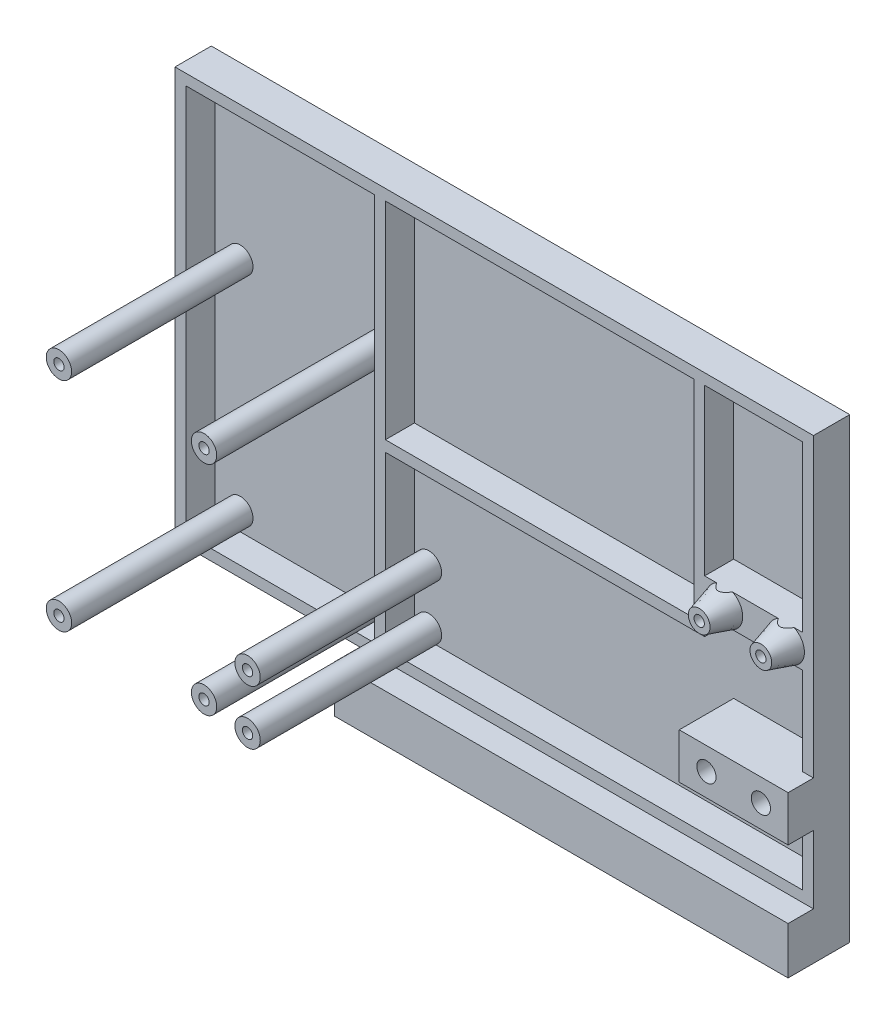
SolidWorks part; units mm, degrees
material "ABS"
ref_plane "Front Plane" through (0, 0, 0) normal (0, 0, 1) x (1, 0, 0)
ref_plane "Top Plane" through (0, 0, 0) normal (0, 1, 0) x (1, 0, 0)
ref_plane "Right Plane" through (0, 0, 0) normal (1, 0, 0) x (0, 0, -1)
sketch "Sketch1" plane through (0, 0, 0) normal (0, 0, 1) x (1, 0, 0)
  line L0 (-45.5, -31.5) -> (-45.5, 31.5) construction
  line L1 (-42.5, -28.5) -> (42.5, -28.5)
  line L2 (-42.5, -28.5) -> (-42.5, 28.5)
  line L3 (-42.5, 28.5) -> (42.5, 28.5)
  line L4 (42.5, -28.5) -> (42.5, 28.5)
  line L5 (-42.5, -28.5) -> (42.5, 28.5) construction
  line L6 (-42.5, 28.5) -> (42.5, -28.5) construction
  line L7 (-45.5, -81.5) -> (75.5, -81.5) construction
  line L8 (-45.5, -81.5) -> (-45.5, -31.5) construction
  line L9 (-45.5, -31.5) -> (75.5, -31.5) construction
  line L10 (75.5, -81.5) -> (75.5, -31.5) construction
  line L11 (-45.5, -81.5) -> (75.5, -31.5) construction
  line L12 (-45.5, -31.5) -> (75.5, -81.5) construction
  line L17 (-45.5, 31.5) -> (45.5, 31.5) construction
  line L18 (45.5, -31.5) -> (45.5, 31.5) construction
  line L19 (-45.5, -31.5) -> (45.5, -31.5) construction
  line L21 (45.5, 31.5) -> (75.5, 31.5) construction
  line L22 (45.5, 31.5) -> (45.5, -31.5) construction
  line L23 (45.5, -31.5) -> (75.5, -31.5) construction
  line L24 (75.5, 31.5) -> (75.5, -31.5) construction
  line L25 (-45.5, 31.5) -> (75.5, 31.5)
  line L26 (-45.5, 31.5) -> (-45.5, -81.5)
  line L27 (-45.5, -81.5) -> (75.5, -81.5)
  line L28 (75.5, 31.5) -> (75.5, -81.5)
  circle A0 centre (68, -56.5) radius 2.65
  circle A1 centre (53, -56.5) radius 2.65
  circle A2 centre (51, -21.5) radius 1.425
  circle A3 centre (68, -21.5) radius 1.425
  point P0 (0, 0)
  point P6 (15, -56.5)
  dimension "D4" = 15
  dimension "D5" = 7.5
  dimension "D6" = 5.3
  dimension "D10" = 2.85
  dimension "D1" = 85
  dimension "D2" = 57
  dimension "D3" = 50
  dimension "D7" = 30
  dimension "D8" = 10
  dimension "D11" = 17
  dimension "D9" = 3
extrude "Boss-Extrude1" add sketch "Sketch1" along normal blind 10
sketch "Sketch2" plane through (0, 0, 0) normal (0, 0, -1) x (-1, 0, 0)
  line L1 (-42.5, 28.5) -> (42.5, 28.5)
  line L2 (-42.5, 28.5) -> (-42.5, -28.5)
  line L3 (-42.5, -28.5) -> (42.5, -28.5)
  line L4 (42.5, 28.5) -> (42.5, -28.5)
extrude "Boss-Extrude2" add sketch "Sketch2" against normal blind 2
sketch "Sketch4" plane through (0, 0, 10) normal (0, 0, 1) x (1, 0, 0)
  line L0 (-42.5, 28.5) -> (-45.5, 31.5) construction
  line L1 (-45.5, 31.5) -> (45.5, 31.5)
  line L2 (-45.5, 31.5) -> (-45.5, -31.5)
  line L3 (-45.5, -31.5) -> (45.5, -31.5)
  line L4 (45.5, 31.5) -> (45.5, -31.5)
  line L5 (42.5, -28.5) -> (45.5, -31.5) construction
  line L6 (-45.5, -31.5) -> (-45.5, -81.5)
  line L7 (-45.5, -81.5) -> (75.5, -81.5)
  line L8 (75.5, -81.5) -> (75.5, 31.5)
  line L9 (75.5, 31.5) -> (45.5, 31.5)
  line L10 (45.5, -31.5) -> (45.5, 31.5)
  line L11 (-45.5, -31.5) -> (45.5, -31.5)
  line L12 (-45.5, -81.5) -> (-45.5, -31.5)
  line L13 (53, -56.5) -> (68, -56.5) construction
  line L14 (-42.5, -28.5) -> (-42.5, -78.5)
  line L15 (45.5, -62.75) -> (75.5, -62.75)
  line L16 (45.5, -62.75) -> (45.5, -50.25)
  line L17 (45.5, -50.25) -> (75.5, -50.25)
  line L18 (75.5, -62.75) -> (75.5, -50.25)
  line L19 (45.5, -62.75) -> (75.5, -50.25) construction
  line L20 (45.5, -50.25) -> (75.5, -62.75) construction
  line L21 (-42.5, -78.5) -> (72.5, -78.5)
  line L22 (72.5, -78.5) -> (72.5, -62.75)
  line L23 (45.5, 28.5) -> (72.5, 28.5)
  line L24 (72.5, 28.5) -> (72.5, -21.5)
  line L25 (72.5, -21.5) -> (72.5, -50.25)
  line L26 (-42.5, -78.5) -> (-45.5, -81.5) construction
  line L27 (72.5, -78.5) -> (75.5, -81.5) construction
  line L28 (72.5, 28.5) -> (75.5, 31.5) construction
  line L29 (51, -21.5) -> (68, -21.5) construction
  line L31 (73.5, -26) -> (45.5, -26)
  line L32 (73.5, -26) -> (73.5, -17)
  line L33 (73.5, -17) -> (45.5, -17)
  line L34 (45.5, -26) -> (45.5, -17)
  line L35 (73.5, -26) -> (45.5, -17) construction
  line L36 (73.5, -17) -> (45.5, -26) construction
  circle A2 centre (53, -56.5) radius 2.65
  circle A3 centre (68, -56.5) radius 2.65
  circle A6 centre (68, -56.5) radius 2.65 construction
  point P21 (60.5, -56.5)
  point P29 (59.5, -21.5)
  dimension "D2" = 9
  dimension "D1" = 12.5
extrude "Cut-Extrude1" cut sketch "Sketch4" against normal up to surface (8 mm away) contours L33 L24 L23 L10 | L25 L31 L4 L11 L14 L21 L22 L15 L16 L17 region at (59, 5.75, 10) region at (13.4057, -54.1556, 10) up to face at (0, 0, 2)
sketch "Sketch5" plane through (0, 0, 0) normal (0, 0, -1) x (-1, 0, 0)
  line L1 (-64.25, -25.25) -> (-71.75, -25.25) construction
  line L2 (-64.25, -25.25) -> (-64.25, -17.75) construction
  line L3 (-64.25, -17.75) -> (-71.75, -17.75) construction
  line L4 (-71.75, -25.25) -> (-71.75, -17.75) construction
  line L5 (-64.25, -25.25) -> (-71.75, -17.75) construction
  line L6 (-64.25, -17.75) -> (-71.75, -25.25) construction
  line L7 (-47.25, -25.25) -> (-54.75, -25.25) construction
  line L8 (-47.25, -25.25) -> (-47.25, -17.75) construction
  line L9 (-47.25, -17.75) -> (-54.75, -17.75) construction
  line L10 (-54.75, -25.25) -> (-54.75, -17.75) construction
  line L11 (-47.25, -25.25) -> (-54.75, -17.75) construction
  line L12 (-47.25, -17.75) -> (-54.75, -25.25) construction
  line L13 (-73.25, -61.75) -> (-62.75, -61.75)
  line L14 (-73.25, -61.75) -> (-73.25, -51.25)
  line L15 (-73.25, -51.25) -> (-62.75, -51.25)
  line L16 (-62.75, -61.75) -> (-62.75, -51.25)
  line L17 (-73.25, -61.75) -> (-62.75, -51.25) construction
  line L18 (-73.25, -51.25) -> (-62.75, -61.75) construction
  line L19 (-47.75, -61.75) -> (-58.25, -61.75)
  line L20 (-47.75, -61.75) -> (-47.75, -51.25)
  line L21 (-47.75, -51.25) -> (-58.25, -51.25)
  line L22 (-58.25, -61.75) -> (-58.25, -51.25)
  line L23 (-47.75, -61.75) -> (-58.25, -51.25) construction
  line L24 (-47.75, -51.25) -> (-58.25, -61.75) construction
  point P0 (-68, -21.5)
  point P6 (-51, -21.5)
  point P12 (-68, -56.5)
  point P18 (-53, -56.5)
  dimension "D1" = 7.5
  dimension "D2" = 10.5
extrude "Cut-Extrude2" cut sketch "Sketch5" against normal blind 7
sketch "Sketch7" plane through (0, 0, 10) normal (0, 0, 1) x (1, 0, 0)
  line L0 (75.5, -81.5) -> (75.5, 31.5) construction
  line L1 (45.5, -50.25) -> (75.5, -50.25)
  line L2 (45.5, -50.25) -> (45.5, -62.75)
  line L3 (45.5, -62.75) -> (75.5, -62.75)
  line L4 (75.5, -50.25) -> (75.5, -62.75)
  line L5 (45.5, -62.75) -> (72.5, -62.75) construction
  circle A0 centre (51, -21.5) radius 1.425
  circle A1 centre (51, -21.5) radius 3
  circle A2 centre (68, -21.5) radius 3
  circle A3 centre (68, -21.5) radius 1.425
  circle A4 centre (53, -56.5) radius 2.65
  circle A5 centre (68, -56.5) radius 2.65
  circle A6 centre (53, -56.5) radius 2.65 construction
  circle A7 centre (51, -21.5) radius 1.425 construction
  dimension "D1" = 6
extrude "Boss-Extrude4" add sketch "Sketch7" along normal blind 7
chamfer "Chamfer2" distance 2 distance2 7 2 edges at (65, -21.5, 10) (48, -21.5, 10) first distance on face at (65, -21.5, 10)
sketch "Sketch9" plane through (0, 0, 0) normal (0, 0, -1) x (-1, 0, 0)
  line L0 (45.5, -81.5) -> (-75.5, -81.5) construction
  line L1 (45.5, 31.5) -> (100.5, 31.5)
  line L2 (45.5, 31.5) -> (45.5, -81.5)
  line L3 (45.5, -81.5) -> (100.5, -81.5)
  line L4 (100.5, 31.5) -> (100.5, -81.5)
  dimension "D1" = 55
extrude "Boss-Extrude5" add sketch "Sketch9" against normal up to surface (17 mm away) up to face at (54, -21.5, 17)
sketch "Sketch10" plane through (0, 0, 17) normal (0, 0, 1) x (1, 0, 0)
  line L1 (-90.5, -73.5) -> (-50.5, -73.5) construction
  line L2 (-90.5, -73.5) -> (-90.5, -13.5) construction
  line L3 (-90.5, -13.5) -> (-50.5, -13.5) construction
  line L4 (-50.5, -73.5) -> (-50.5, -13.5) construction
  line L5 (-90.5, -73.5) -> (-50.5, -13.5) construction
  line L6 (-90.5, -13.5) -> (-50.5, -73.5) construction
  line L7 (-45.5, 31.5) -> (-45.5, -81.5) construction
  line L8 (-45.5, -78.5) -> (-95.5, -78.5) construction
  line L9 (-45.5, -78.5) -> (-45.5, -8.5) construction
  line L10 (-45.5, -8.5) -> (-95.5, -8.5) construction
  line L11 (-95.5, -78.5) -> (-95.5, -8.5) construction
  line L12 (-45.5, -78.5) -> (-95.5, -8.5) construction
  line L13 (-45.5, -8.5) -> (-95.5, -78.5) construction
  line L14 (-45.5, 31.5) -> (-45.5, -81.5) construction
  circle A0 centre (-90.5, -13.5) radius 1.425
  circle A1 centre (-50.5, -13.5) radius 1.425
  circle A2 centre (-90.5, -73.5) radius 1.425
  circle A3 centre (-50.5, -73.5) radius 1.425
  point P0 (-70.5, -43.5)
  point P9 (-70.5, -43.5)
  point P14 (0, 0)
  point P16 (-45.5, -81.5)
  point P17 (-45.5, -76.7867)
  point P21 (0, 0)
  dimension "D3" = 2.85
  dimension "D1" = 60
  dimension "D2" = 40
  dimension "D4" = 50
  dimension "D5" = 70
extrude "Cut-Extrude3" cut sketch "Sketch10" against normal through all
sketch "Sketch11" plane through (0, 0, 17) normal (0, 0, 1) x (1, 0, 0)
  line L0 (-48.5, 28.5) -> (-45.5, 28.5)
  line L1 (-45.5, 31.5) -> (-45.5, -81.5) construction
  line L2 (-48.5, -78.5) -> (-45.5, -78.5)
  line L3 (-45.5, 31.5) -> (-45.5, -81.5) construction
  line L4 (-45.5, -78.5) -> (-45.5, 28.5)
  line L8 (-48.5, -78.5) -> (-48.5, 28.5)
  line L9 (-48.5, 28.5) -> (-97.5, 28.5)
  line L10 (-97.5, 28.5) -> (-97.5, -78.5)
  line L11 (-97.5, -78.5) -> (-48.5, -78.5)
  line L12 (-48.5, -78.5) -> (-48.5, 28.5) construction
  line L13 (-48.5, 28.5) -> (-97.5, 28.5)
  line L14 (-97.5, 28.5) -> (-97.5, -78.5)
  line L15 (-97.5, -78.5) -> (-48.5, -78.5)
  circle A0 centre (-90.5, -13.5) radius 3.5
  circle A1 centre (-50.5, -13.5) radius 3.5
  circle A2 centre (-90.5, -73.5) radius 3.5
  circle A3 centre (-50.5, -73.5) radius 3.5
  line M10 (-45.5, -81.5) -> (-45.5, 31.5)
  dimension "D1" = 7
  dimension "D2" = 3
extrude "Cut-Extrude4" cut sketch "Sketch11" against normal up to surface (15 mm away) contours L15 L12 L13 A1 A0 L14 A2 A3 | L12 L2 L0 M10 region at (-46.9653, -24.2757, 17) region at (-73.0159, -24.4856, 17) up to face at (0, 0, 2)
sketch "Sketch12" plane through (0, 0, 17) normal (0, 0, 1) x (1, 0, 0)
  line L5 (-100.5, -81.5) -> (-45.5, -81.5)
  line L6 (-100.5, -81.5) -> (-100.5, 31.5)
  line L7 (-100.5, 31.5) -> (-45.5, 31.5)
  line L8 (-45.5, -81.5) -> (-45.5, 31.5)
  circle A0 centre (-90.5, -13.5) radius 3.5
  circle A1 centre (-50.5, -13.5) radius 3.5
  circle A2 centre (-90.5, -73.5) radius 3.5
  circle A3 centre (-50.5, -73.5) radius 3.5
  circle A4 centre (-90.5, -73.5) radius 3.5 construction
extrude "Cut-Extrude5" cut sketch "Sketch12" against normal up to surface (7 mm away) up to face at (37.0833, -29.625, 10)
sketch "Sketch14" plane through (0, 0, 2) normal (0, 0, 1) x (1, 0, 0)
  line L8 (-38.5, -75.5) -> (-38.5, -60.5) construction
  line L9 (-42.5, -78.5) -> (-21.5, -78.5) construction
  line L10 (-42.5, -78.5) -> (-42.5, -57.5) construction
  line L11 (-42.5, -57.5) -> (-21.5, -57.5) construction
  line L12 (-21.5, -78.5) -> (-21.5, -57.5) construction
  line L13 (-42.5, -78.5) -> (-21.5, -57.5) construction
  line L14 (-42.5, -57.5) -> (-21.5, -78.5) construction
  circle A0 centre (-38.5, -60.5) radius 1.275
  circle A1 centre (-38.5, -75.5) radius 1.275
  point P0 (-32, -68)
  point P9 (-38.5, -68)
  dimension "D3" = 2.55
  dimension "D1" = 21
  dimension "D2" = 15
  dimension "D4" = 4
extrude "Cut-Extrude6" cut sketch "Sketch14" against normal through all both and the other way through all
sketch "Sketch13" plane through (0, -81.5, 0) normal (0, -1, 0) x (1, 0, 0)
  line L0 (71.5, 4) -> (-45.5, 4) construction
  line L1 (-49.5, 0) -> (75.5, 0)
  line L2 (-49.5, 0) -> (-49.5, 17)
  line L3 (-49.5, 17) -> (75.5, 17)
  line L4 (75.5, 0) -> (75.5, 17)
  line L5 (42.25, 4) -> (-16.25, 4) construction
  line L6 (-100.5, 0) -> (75.5, 0) construction
  line L7 (13, 4) -> (-16.25, 4) construction
  line L8 (-16.25, 4) -> (-45.5, 4) construction
  circle A0 centre (71.5, 4) radius 4 construction
  circle A1 centre (-45.5, 4) radius 4 construction
  circle A2 centre (-16.25, 4) radius 1.9
  circle A3 centre (42.25, 4) radius 1.9
  circle A4 centre (71.5, 4) radius 1.9
  circle A5 centre (-45.5, 4) radius 1.9
  point P9 (13, 4)
  point P12 (13, 4)
  dimension "D1" = 8
  dimension "D3" = 3.8
  dimension "D2" = 125
extrude "Boss-Extrude6" add sketch "Sketch13" along normal blind 13
sketch "Sketch15" plane through (0, 0, 2) normal (0, 0, 1) x (1, 0, 0)
  circle A0 centre (-38.5, -60.5) radius 3.5
  circle A1 centre (-38.5, -75.5) radius 3.5
  circle A2 centre (-38.5, -60.5) radius 1.275
  circle A3 centre (-38.5, -75.5) radius 1.275
  circle A4 centre (-38.5, -60.5) radius 1.275 construction
  dimension "D1" = 7
extrude "Boss-Extrude7" add sketch "Sketch15" along normal up to surface (15 mm away) up to face at (-49.075, -73.5, 17)
sketch "Sketch16" plane through (0, 0, 17) normal (0, 0, 1) x (1, 0, 0)
  circle A0 centre (-90.5, -13.5) radius 1.425
  circle A1 centre (-50.5, -13.5) radius 1.425
  circle A2 centre (-90.5, -73.5) radius 1.425
  circle A3 centre (-50.5, -73.5) radius 1.425
  circle A4 centre (-38.5, -60.5) radius 1.425
  circle A5 centre (-38.5, -75.5) radius 1.425
  circle A6 centre (-90.5, -73.5) radius 1.425 construction
  circle A7 centre (-90.5, -13.5) radius 3.5
  circle A8 centre (-50.5, -13.5) radius 3.5
  circle A9 centre (-38.5, -60.5) radius 3.5
  circle A10 centre (-38.5, -75.5) radius 3.5
  circle A11 centre (-50.5, -73.5) radius 3.5
  circle A12 centre (-90.5, -73.5) radius 3.5
  circle A13 centre (-90.5, -13.5) radius 3.5 construction
extrude "Boss-Extrude8" add sketch "Sketch16" along normal blind 35
